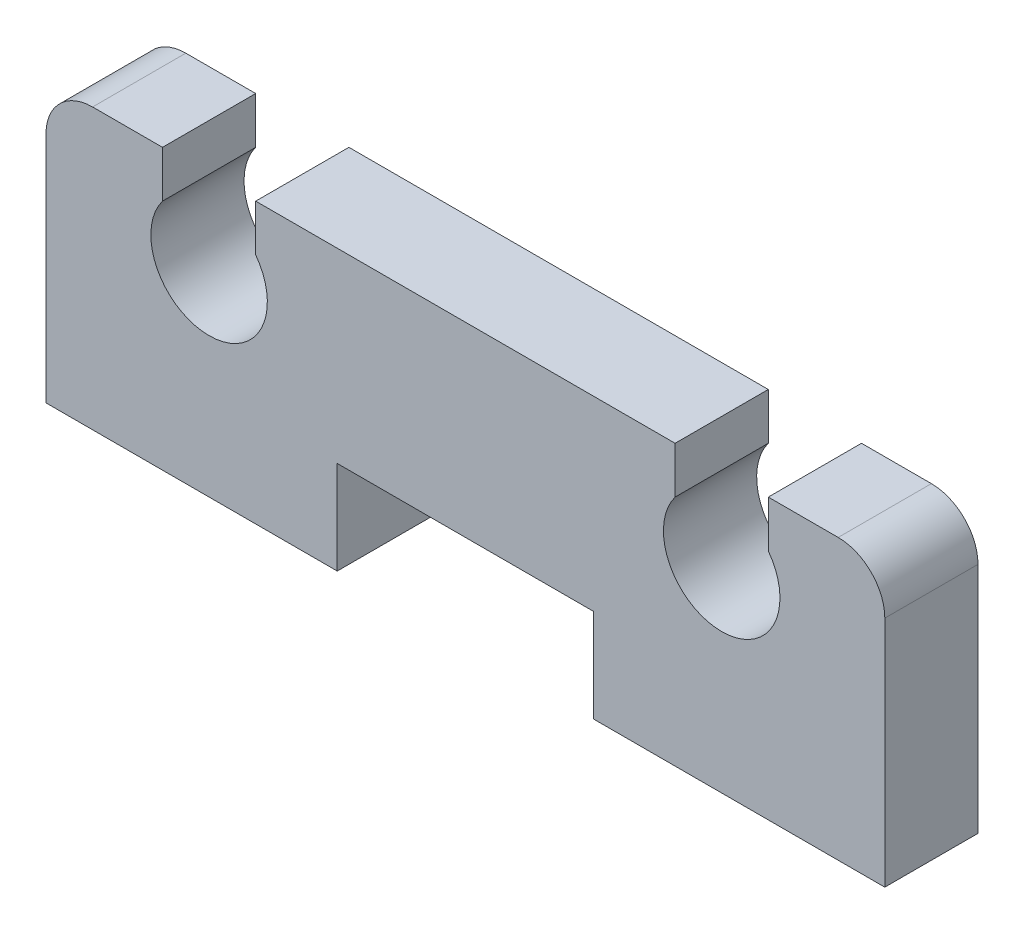
SolidWorks part; units mm, degrees
ref_plane "Front Plane" through (0, 0, 0) normal (0, 0, 1) x (1, 0, 0)
ref_plane "Top Plane" through (0, 0, 0) normal (0, 1, 0) x (1, 0, 0)
ref_plane "Right Plane" through (0, 0, 0) normal (1, 0, 0) x (0, 0, -1)
sketch "Sketch1" plane through (0, 0, 0) normal (0, 0, 1) x (1, 0, 0)
  line L14 (-9, 0) -> (-9, 6)
  line L15 (-9, 6) -> (-6.5, 6)
  line L16 (-9, 0) -> (-2.75, 0)
  line L17 (-2.75, 0) -> (-2.75, 2)
  line L18 (-2.75, 2) -> (2.75, 2)
  line L19 (0, 6) -> (0, 0) construction
  line L20 (-6.5, 5) -> (-6.5, 6)
  line L21 (-4.5, 5) -> (-4.5, 6)
  line L22 (-4.5, 6) -> (4.5, 6)
  line L23 (4.5, 5) -> (4.5, 6)
  line L24 (6.5, 5) -> (6.5, 6)
  line L25 (2.75, 0) -> (2.75, 2)
  line L26 (9, 0) -> (2.75, 0)
  line L27 (9, 6) -> (6.5, 6)
  line L28 (9, 0) -> (9, 6)
  arc A4 (-6.5, 5) -> (-4.5, 5) centre (-5.5, 4.25) ccw
  arc A5 (6.5, 5) -> (4.5, 5) centre (5.5, 4.25) cw
  point P41 (0, 2)
  dimension "D2" = 9
  dimension "D10" = 1.25
  dimension "D3" = 2
  dimension "D4" = 1.75
  dimension "D5" = 2
  dimension "D6" = 6
  dimension "D7" = 6.25
  dimension "D9" = 3.5
extrude "Tube Plate Body" add sketch "Sketch1" along normal blind 2
fillet "Tube Plate Contouring" radius 1 2 edges at (9, 6, 1) (-9, 6, 1)
equation "\"D2@Sketch1\"=\"Wph@Parameters@RobotHandParameters.SLDPRT\"/2"
equation "\"D6@Sketch1\"=\"rd@Parameters@RobotHandParameters.SLDPRT\" - 2 - \"Tjointd@Parameters@RobotHandParameters.SLDPRT\"/2 + 1.75"
